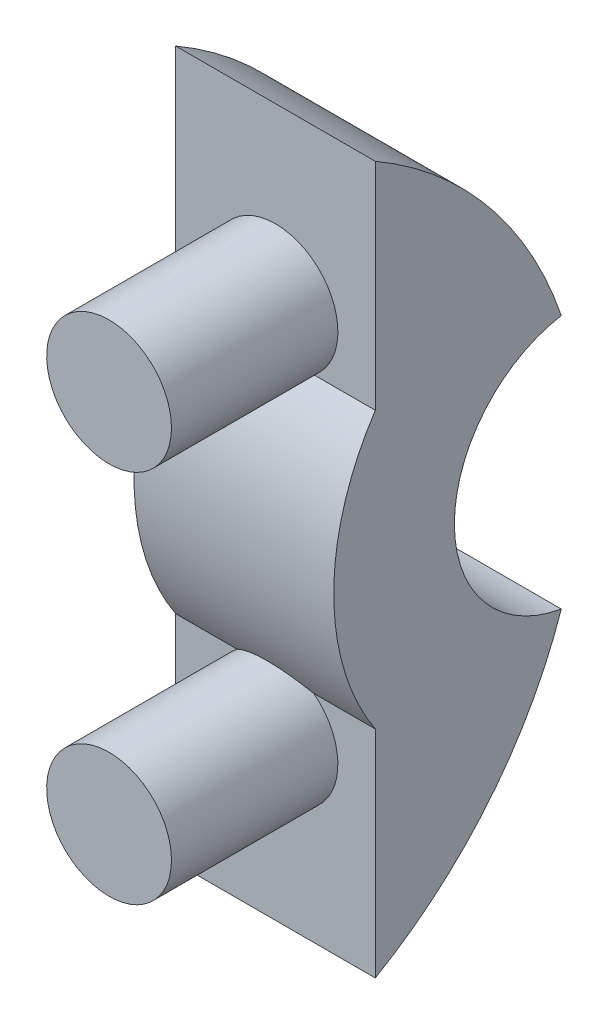
SolidWorks part; units mm, degrees
ref_plane "前视基准面" through (0, 0, 0) normal (0, 0, 1) x (1, 0, 0)
ref_plane "上视基准面" through (0, 0, 0) normal (0, 1, 0) x (1, 0, 0)
ref_plane "右视基准面" through (0, 0, 0) normal (1, 0, 0) x (0, 0, -1)
sketch "草图1" plane through (0, 0, 0) normal (0, 0, 1) x (1, 0, 0)
  line L1 (0, 0) -> (4.8, 0)
  line L2 (0, 0) -> (0, 17)
  line L3 (0, 17) -> (4.8, 17)
  line L4 (4.8, 0) -> (4.8, 17)
extrude "凸台-拉伸1" add sketch "草图1" along normal blind 5
sketch "草图2" plane through (4.8, 0, 0) normal (1, 0, 0) x (0, 0, -1)
  line L0 (0, 0) -> (0, 17) construction
  circle A0 centre (0, 8.5) radius 3.1
extrude "切除-拉伸1" cut sketch "草图2" against normal through all
sketch "草图3" plane through (4.8, 0, 0) normal (1, 0, 0) x (0, 0, -1)
  line L0 (-5, 0) -> (-5, 17) construction
  line L1 (-5, 11.8166) -> (-5, 5.1834)
  arc A0 (-5, 11.8166) -> (-5, 5.1834) centre (0, 8.5) ccw
extrude "凸台-拉伸2" add sketch "草图3" against normal blind 4.8
fillet "圆角1" radius 10 2 edges at (2.4, 0, 0) (2.4, 17, 0)
sketch "草图4" plane through (0, 0, 5) normal (0, 0, 1) x (1, 0, 0)
  circle A0 centre (2.4, 13) radius 1.5
  circle A1 centre (2.4, 4) radius 1.5
extrude "凸台-拉伸3" add sketch "草图4" along normal blind 4
